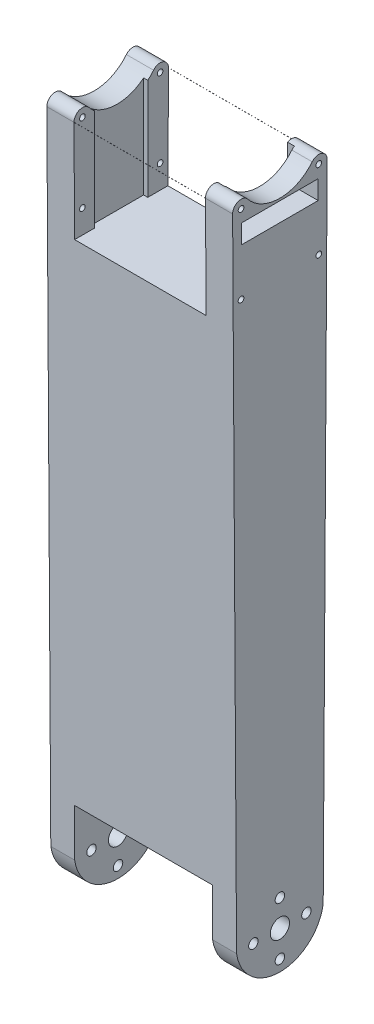
SolidWorks part; units mm, degrees
ref_plane "Front Plane" through (0, 0, 0) normal (0, 0, 1) x (1, 0, 0)
ref_plane "Top Plane" through (0, 0, 0) normal (0, 1, 0) x (1, 0, 0)
ref_plane "Right Plane" through (0, 0, 0) normal (1, 0, 0) x (0, 0, -1)
sketch "Sketch1" plane through (0, 0, 0) normal (1, 0, 0) x (0, 0, -1)
  line L0 (55.88, 0) -> (-55.88, 0) construction
  line L1 (-32.73, 0) -> (12.5, 0) construction
  line L2 (-32.73, 0) -> (-32.73, -36.5) construction
  line L3 (-32.73, -36.5) -> (12.5, -36.5) construction
  line L4 (12.5, 0) -> (12.5, -36.5) construction
  line L5 (0, 38.1) -> (0, 215.9) construction
  line L6 (-50.8, 0) -> (50.8, 0) construction
  line L7 (-50.8, 0) -> (-50.8, -50.8) construction
  line L8 (-50.8, -50.8) -> (50.8, -50.8) construction
  line L9 (50.8, 0) -> (50.8, -50.8) construction
  line L10 (0, 55.88) -> (0, -55.88) construction
  line L11 (0, 215.9) -> (-75.29, 422.7577) construction
  line L12 (-67.0833, 436.5088) -> (-90.4159, 428.0165) construction
  line L13 (12.415, 180.785) -> (-12.415, 180.785) construction
  line L18 (12.415, 180.785) -> (12.415, 226.015) construction
  line L19 (-12.415, 180.785) -> (-12.415, 226.015) construction
  line L20 (12.415, 226.015) -> (-12.415, 226.015) construction
  line L21 (0, 215.9) -> (0, 180.785) construction
  line L22 (0, 203.4) -> (-12.415, 203.4) construction
  line L27 (-67.0833, 436.5088) -> (-51.6137, 394.0065) construction
  line L28 (-90.4159, 428.0165) -> (-74.9463, 385.5142) construction
  line L29 (-51.6137, 394.0065) -> (-74.9463, 385.5142) construction
  line L30 (-59.3485, 415.2577) -> (-82.6811, 406.7653) construction
  line L31 (-75.29, 422.7577) -> (-133.6626, 471.7381) construction
  line L33 (-12.415, 50.6) -> (12.415, 50.6) construction
  line L34 (-12.415, 50.6) -> (-12.415, 5.37) construction
  line L35 (-12.415, 5.37) -> (12.415, 5.37) construction
  line L36 (12.415, 50.6) -> (12.415, 5.37) construction
  circle A0 centre (0, 38.1) radius 3 construction
  circle A1 centre (0, 215.9) radius 3 construction
  circle A3 centre (-75.29, 422.7577) radius 3 construction
  point P6 (-10.115, -36.5)
  point P9 (0, -50.8)
  point P25 (-12.5, 38.1)
  point P27 (0, 203.4)
  point P42 (-63.28, 389.7604)
  point P47 (0, 5.37)
  dimension "D15" = 6
  dimension "D8" = 0
  dimension "D12" = 12.5
  dimension "D1" = 36.5
  dimension "D2" = 45.23
  dimension "D3" = 101.6
  dimension "D4" = 50.8
  dimension "D5" = 38.1
  dimension "D6" = 177.8
  dimension "D7" = 220.1333
  dimension "D9" = 24.83
  dimension "D10" = 12.5
  dimension "D11" = 12.5
  dimension "D13" = 76.2
  dimension "D14" = 160
  dimension "D16" = 12.5
  dimension "D17" = 150
  dimension "D18" = 12.5
sketch "Sketch2" plane through (0, 0, 0) normal (0, 0, 1) x (1, 0, 0)
  line L6 (55.88, 0) -> (-55.88, 0) construction
  line L7 (-50.8, 0) -> (50.8, 0) construction
  line L8 (-50.8, 0) -> (-50.8, -50.8) construction
  line L9 (-50.8, -50.8) -> (50.8, -50.8) construction
  line L10 (50.8, 0) -> (50.8, -50.8) construction
  dimension "D1" = 101.6
sketch "Sketch3" plane through (0, 0, 0) normal (1, 0, 0) x (0, 0, -1)
  line L0 (-11.4298, 38.0297) -> (-12.4725, 207.5865)
  line L1 (-10.25, 9.1002) -> (10.25, 9.1002) construction
  line L3 (-10.25, 186.9002) -> (10.25, 186.9002) construction
  line L4 (0, 215.9) -> (-75.29, 422.7577) construction
  line L5 (12.4725, 207.5865) -> (11.4298, 38.0297)
  circle A0 centre (0, 38.1) radius 10
  circle A1 centre (-10.25, 9.1002) radius 0.7501
  circle A2 centre (10.25, 9.1002) radius 0.7501
  circle A3 centre (10.25, 29.8002) radius 0.7501
  circle A4 centre (-10.25, 29.8002) radius 0.7501
  circle A5 centre (0, 45.1) radius 1.2501
  circle A6 centre (7, 38.1) radius 1.2501
  circle A7 centre (0, 31.1) radius 1.2501
  circle A8 centre (-7, 38.1) radius 1.2501
  circle A9 centre (-10.25, 186.9002) radius 0.7501
  circle A10 centre (10.25, 186.9002) radius 0.7501
  circle A11 centre (10.25, 207.6001) radius 0.7501
  circle A12 centre (-10.25, 207.6001) radius 0.7501
  circle A13 centre (0, 215.9) radius 10 construction
  arc A14 (-8.5228, 208.9988) -> (8.5228, 208.9988) centre (0, 215.9) ccw
  arc A16 (8.5228, 208.9988) -> (12.4725, 207.5865) centre (10.25, 207.6001) cw
  arc A17 (-11.4298, 38.0297) -> (11.4298, 38.0297) centre (0, 38.1) ccw
  circle A18 centre (0, 38.1) radius 2.54
  arc A19 (-8.5228, 208.9988) -> (-12.4725, 207.5865) centre (-10.25, 207.6001) ccw
  arc A20 (11.4298, 38.0297) -> (-11.4298, 38.0297) centre (0, 39.6431) cw
  point P5 (0, 186.9002)
  point P16 (0, 9.1002)
  dimension "D1" = 1.5001
  dimension "D9" = 20
  dimension "D12" = 2.5001
  dimension "D13" = 20.7
  dimension "D16" = 0
  dimension "D17" = 5.08
  dimension "D18" = 11.43
  dimension "D19" = 2.2225
  dimension "D4" = 13.189
  dimension "D5" = 28.9998
  dimension "D6" = 20.5001
  dimension "D7" = 20.7
  dimension "D8" = 28.9998
  dimension "D10" = 7
  dimension "D14" = 20.5
  dimension "D15" = 13.189
  dimension "D2" = 2
  dimension "D3" = 2
  dimension "D11" = 4
extrude "Boss-Extrude1" add sketch "Sketch3" along normal blind 24.511 and the other way blind 24.511 contours A17 L5 A16 A14 A19 L0
extrude "Cut-Extrude3" cut sketch "Sketch3<4>" against normal through all and the other way through all contours A8 | A5 | A6 | A7 | A9 | A10 | A11 | A12 | A18
sketch "Sketch3<4>" plane through (0, 0, 0) normal (1, 0, 0) x (0, 0, -1) same geometry as "Sketch3"
sketch "Sketch4" plane through (0, 0, 0) normal (1, 0, 0) x (0, 0, -1)
  line L0 (-12.415, 50.6) -> (12.415, 50.6) construction
  line L1 (-11.5071, 50.6) -> (11.5071, 50.6)
  line L2 (-11.5071, 50.6) -> (-11.5071, 26.67)
  line L3 (-11.5071, 26.67) -> (11.5071, 26.67)
  line L4 (11.5071, 50.6) -> (11.5071, 26.67)
  line L5 (-11.4298, 38.0297) -> (-12.4725, 207.5865) construction
  line L6 (12.4725, 207.5865) -> (11.4298, 38.0297) construction
  line L8 (-12.4725, 180.7002) -> (12.4725, 180.7002)
  line L9 (-12.4725, 180.7002) -> (-12.4725, 209.8226)
  line L10 (-12.4725, 209.8226) -> (12.4725, 209.8226)
  line L11 (12.4725, 180.7002) -> (12.4725, 209.8226)
  arc A0 (-11.4298, 38.0297) -> (11.4298, 38.0297) centre (0, 38.1) ccw construction
  arc A2 (-8.5228, 208.9988) -> (-12.4725, 207.5865) centre (-10.25, 207.6001) ccw construction
  dimension "D1" = 6.2
extrude "Cut-Extrude4" cut sketch "Sketch4" against normal blind 18.2 and the other way blind 18.2 contours L4 L1 L2 L3 region at (0, 38.635, 0)
extrude "Cut-Extrude5" cut sketch "Sketch4<4>" against normal blind 17.35 and the other way blind 17.35 contours L8 L11 L10 L9 region at (0, 195.2614, 0)
sketch "Sketch4<4>" plane through (0, 0, 0) normal (1, 0, 0) x (0, 0, -1) same geometry as "Sketch4"
sketch "Sketch5" plane through (17.35, 0, 0) normal (-1, 0, 0) x (0, 0, 1)
  line L0 (-11.9981, 210.6001) -> (-11.9981, 208.7639)
  line L1 (-11.9981, 206.4364) -> (-11.9981, 184.2639)
  line L2 (-9.6037, 181.1021) -> (9.6037, 181.1021)
  line L3 (11.9981, 184.2639) -> (11.9981, 206.4364)
  line L4 (11.9981, 208.7639) -> (11.9981, 210.6001)
  line L5 (11.9981, 210.6001) -> (9.645, 210.6001)
  line L6 (6.5, 207.0195) -> (6.5, 204.3501)
  line L7 (6.5, 204.3501) -> (10.1, 204.3501)
  line L8 (10.1, 204.3501) -> (10.1, 199.3501)
  line L9 (10.1, 199.3501) -> (9.2, 199.3501)
  line L10 (9.2, 199.3501) -> (9.2, 186.0001)
  line L11 (9.2, 186.0001) -> (-9.2, 186.0001)
  line L12 (-9.2, 186.0001) -> (-9.2, 199.3501)
  line L13 (-9.2, 199.3501) -> (-10.1, 199.3501)
  line L14 (-10.1, 199.3501) -> (-10.1, 204.3501)
  line L15 (-10.1, 204.3501) -> (-6.5, 204.3501)
  line L16 (-6.5, 204.3501) -> (-6.5, 207.0195)
  line L17 (-9.645, 210.6001) -> (-11.9981, 210.6001)
  line L19 (-10.1, 204.3501) -> (10.1, 204.3501)
  line L20 (-10.1, 204.3501) -> (-10.1, 199.3501)
  line L21 (-10.1, 199.3501) -> (10.1, 199.3501)
  line L22 (10.1, 204.3501) -> (10.1, 199.3501)
  line L23 (9.2, 186.0001) -> (-9.2, 186.0001)
  line L24 (9.2, 186.0001) -> (9.2, 199.3501)
  line L25 (9.2, 199.3501) -> (-9.2, 199.3501)
  line L26 (-9.2, 186.0001) -> (-9.2, 199.3501)
  line L27 (-9.2, 199.3501) -> (9.2, 199.3501)
  line L28 (-9.2, 199.3501) -> (-9.2, 210.6001)
  line L29 (-9.2, 210.6001) -> (9.2, 210.6001)
  line L30 (9.2, 199.3501) -> (9.2, 210.6001)
  arc A0 (-11.9981, 208.7639) -> (-11.9981, 206.4364) centre (-10.25, 207.6001) ccw
  arc A1 (-11.9981, 184.2639) -> (-9.6037, 181.1021) centre (-10.25, 183.1001) ccw
  arc A2 (9.6037, 181.1021) -> (11.9981, 184.2639) centre (10.25, 183.1001) ccw
  arc A3 (11.9981, 206.4364) -> (11.9981, 208.7639) centre (10.25, 207.6001) ccw
  arc A4 (6.5, 207.0195) -> (9.645, 210.6001) centre (0, 215.9001) ccw
  arc A5 (-9.645, 210.6001) -> (-6.5, 207.0195) centre (0, 215.9001) ccw
  point P32 (0, 0)
  arc M30 (12.4725, 207.6138) -> (8.5228, 208.9988) centre (10.25, 207.6001) ccw
  arc M31 (8.5228, 208.9988) -> (-8.5228, 208.9988) centre (0, 215.9) cw
  arc M32 (-8.5228, 208.9988) -> (-12.4725, 207.6138) centre (-10.25, 207.6001) ccw
extrude "Cut-Extrude6" cut sketch "Sketch5" against normal blind 18.2 contours L20 L19 L22 L21
extrude "Cut-Extrude7" cut sketch "Sketch5<3>" against normal blind 1.8 contours L21 L12 L11 L10 | A5 L16 L19 L6 A4 M32 M30 M31 | A5 L28 L19 L16 M32 | A4 L6 L7 L30 M30 region at (17.35, 206.3775, -8.0053) region at (17.35, 209.128, -8.6612) region at (17.35, 192.6751, 0) region at (17.35, 206.3775, 8.0053)
sketch "Sketch5<3>" plane through (17.35, 0, 0) normal (-1, 0, 0) x (0, 0, 1) same geometry as "Sketch5"
sketch "Sketch6" plane through (-17.35, 0, 0) normal (1, 0, 0) x (0, 0, -1)
  line L0 (-12.3071, 180.7002) -> (12.3071, 180.7002) construction
  line L1 (7, 180.7002) -> (-7, 180.7002)
  line L2 (7, 180.7002) -> (7, 209.8226)
  line L3 (7, 209.8226) -> (-7, 209.8226)
  line L4 (-7, 180.7002) -> (-7, 209.8226)
  arc A0 (-8.5228, 208.9988) -> (-12.4725, 207.6138) centre (-10.25, 207.6001) ccw construction
  point P6 (0, 180.7002)
  point P7 (0, 0)
  point P8 (0, 209.8226)
  dimension "D1" = 14
extrude "Cut-Extrude8" cut sketch "Sketch6" against normal blind 1.1
extrude "Cut-Extrude10" cut sketch "Sketch3<5>" against normal through all and the other way through all contours A17 A20 region at (0, 30.7364, 7.7377)
sketch "Sketch3<5>" plane through (0, 0, 0) normal (1, 0, 0) x (0, 0, -1) same geometry as "Sketch3"
